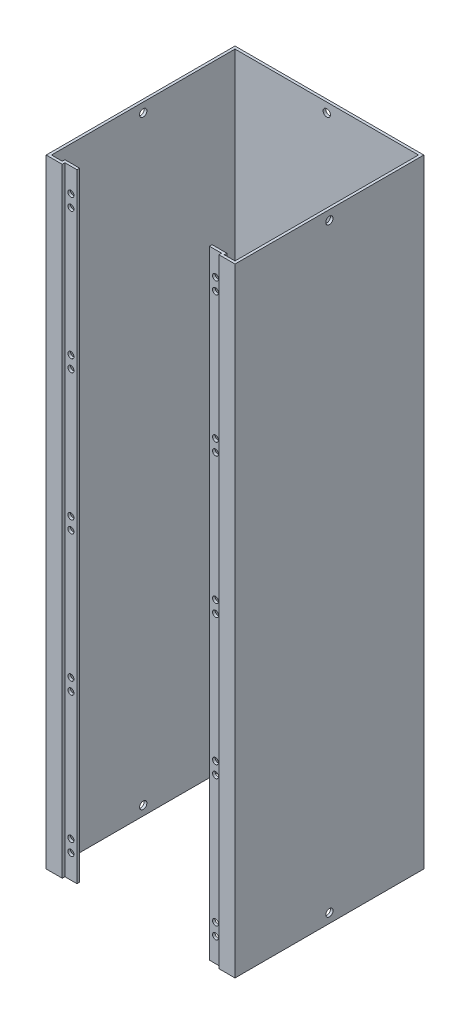
SolidWorks part; units mm, degrees
ref_plane "Front Plane" through (0, 0, 0) normal (0, 0, 1) x (1, 0, 0)
ref_plane "Top Plane" through (0, 0, 0) normal (0, 1, 0) x (1, 0, 0)
ref_plane "Right Plane" through (0, 0, 0) normal (1, 0, 0) x (0, 0, -1)
sketch "Sketch1" plane through (0, 0, 0) normal (0, 1, 0) x (1, 0, 0)
  line L0 (0, 0) -> (0, 100)
  line L1 (0, 100) -> (100, 100)
  line L2 (100, 100) -> (100, 0)
  line L3 (100, 0) -> (91.5, 0)
  line L4 (91.5, 0) -> (91.5, 1.397)
  line L5 (91.5, 1.397) -> (85.1, 1.397)
  line L6 (85.1, 1.397) -> (85.1, 2.794)
  line L7 (85.1, 2.794) -> (92.897, 2.794)
  line L8 (92.897, 2.794) -> (92.897, 1.397)
  line L9 (92.897, 1.397) -> (98.603, 1.397)
  line L10 (98.603, 1.397) -> (98.603, 98.603)
  line L11 (98.603, 98.603) -> (1.397, 98.603)
  line L12 (1.397, 98.603) -> (1.397, 1.397)
  line L13 (1.397, 1.397) -> (7.103, 1.397)
  line L14 (7.103, 1.397) -> (7.103, 2.794)
  line L15 (7.103, 2.794) -> (14.9, 2.794)
  line L16 (14.9, 2.794) -> (14.9, 1.397)
  line L17 (14.9, 1.397) -> (8.5, 1.397)
  line L18 (8.5, 1.397) -> (8.5, 0)
  line L19 (8.5, 0) -> (0, 0)
  dimension "D1" = 8.5
  dimension "D2" = 8.5
  dimension "D3" = 100
  dimension "D4" = 100
  dimension "D5" = 1.397
  dimension "D6" = 1.397
  dimension "D7" = 1.397
  dimension "D8" = 1.397
  dimension "D9" = 1.397
  dimension "D10" = 1.397
  dimension "D11" = 1.397
  dimension "D12" = 1.397
  dimension "D13" = 1.397
  dimension "D14" = 14.9
  dimension "D15" = 14.9
  dimension "D16" = 0
  dimension "D17" = 0
extrude "Boss-Extrude1" add sketch "Sketch1" along normal blind 327.5
sketch "Sketch2" plane through (0, 0, -1.397) normal (0, 0, 1) x (1, 0, 0)
  line L0 (8.5, 327.5) -> (14.9, 327.5) construction
  line L1 (14.9, 327.5) -> (14.9, 0) construction
  line L2 (85.1, 327.5) -> (85.1, 0) construction
  line L3 (85.1, 327.5) -> (91.5, 327.5) construction
  line L4 (8.5, 0) -> (14.9, 0) construction
  circle A0 centre (11.7, 314.9) radius 1.6
  circle A1 centre (11.7, 308.5) radius 1.6
  circle A2 centre (88.3, 314.9) radius 1.6
  circle A3 centre (88.3, 308.5) radius 1.6
  circle A4 centre (11.7, 240.925) radius 1.6
  circle A5 centre (11.7, 234.525) radius 1.6
  circle A6 centre (88.3, 240.925) radius 1.6
  circle A7 centre (88.3, 234.525) radius 1.6
  circle A8 centre (11.7, 166.95) radius 1.6
  circle A9 centre (11.7, 160.55) radius 1.6
  circle A10 centre (88.3, 166.95) radius 1.6
  circle A11 centre (88.3, 160.55) radius 1.6
  circle A12 centre (11.7, 92.975) radius 1.6
  circle A13 centre (11.7, 86.575) radius 1.6
  circle A14 centre (88.3, 92.975) radius 1.6
  circle A15 centre (88.3, 86.575) radius 1.6
  circle A16 centre (11.7, 19) radius 1.6
  circle A17 centre (11.7, 12.6) radius 1.6
  circle A18 centre (88.3, 19) radius 1.6
  circle A19 centre (88.3, 12.6) radius 1.6
  dimension "D1" = 3.2
  dimension "D2" = 3.2
  dimension "D3" = 12.6
  dimension "D4" = 6.4
  dimension "D5" = 3.2
  dimension "D6" = 3.2
  dimension "D8" = 3.2
  dimension "D9" = 3.2
  dimension "D10" = 12.6
  dimension "D12" = 12.6
  dimension "D7" = 2
  dimension "D11" = 5
extrude "Cut-Extrude2" cut sketch "Sketch2" against normal blind 10
sketch "Sketch3" plane through (100, 0, 0) normal (1, 0, 0) x (0, 0, -1)
  line L0 (0, 327.5) -> (100, 327.5) construction
  line L1 (0, 327.5) -> (0, 0) construction
  line L2 (100, 327.5) -> (100, 0) construction
  line L3 (0, 0) -> (100, 0) construction
  circle A0 centre (50, 322.524) radius 1.93
  circle A1 centre (50, 4.976) radius 1.93
  dimension "D1" = 3.86
  dimension "D7" = 3.86
  dimension "D2" = 4.976
  dimension "D3" = 50
  dimension "D4" = 50
  dimension "D5" = 50
  dimension "D6" = 4.976
extrude "Cut-Extrude3" cut sketch "Sketch3" against normal blind 100
sketch "Sketch4" plane through (0, 0, -100) normal (0, 0, -1) x (-1, 0, 0)
  line L0 (-100, 327.5) -> (0, 327.5) construction
  line L1 (0, 327.5) -> (0, 0) construction
  line L2 (-100, 0) -> (0, 0) construction
  circle A0 centre (-50, 322.524) radius 1.93
  circle A1 centre (-50, 4.976) radius 1.93
  dimension "D1" = 3.86
  dimension "D2" = 3.86
  dimension "D3" = 4.976
  dimension "D4" = 50
  dimension "D5" = 4.976
  dimension "D6" = 50
extrude "Cut-Extrude4" cut sketch "Sketch4" against normal blind 10
